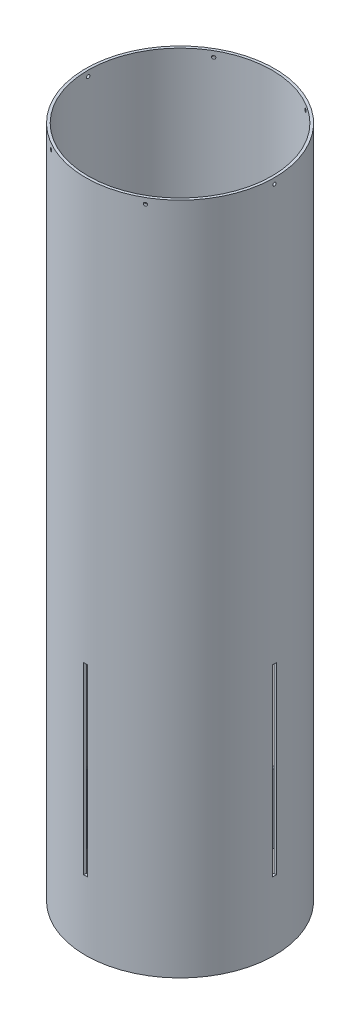
SolidWorks part; units mm, degrees
material "A-Glass Fiber"
ref_plane "Front Plane" through (0, 0, 0) normal (0, 0, 1) x (1, 0, 0)
ref_plane "Top Plane" through (0, 0, 0) normal (0, 1, 0) x (1, 0, 0)
ref_plane "Right Plane" through (0, 0, 0) normal (1, 0, 0) x (0, 0, -1)
sketch "Sketch1" plane through (0, 0, 0) normal (0, 1, 0) x (1, 0, 0)
  circle A0 centre (0, 0) radius 76.2
  circle A1 centre (0, 0) radius 78.359
  dimension "D1" = 152.4
  dimension "D2" = 156.718
extrude "Boss-Extrude1" add sketch "Sketch1" along normal blind 558.8
ref_plane "Plane1" through (0, 0, 0) normal (0.7071, 0, 0.7071) x (0.7071, 0, -0.7071)
ref_axis "Axis1" through (0, 558.8, 0) along (0, -1, 0)
sketch "Sketch2" plane through (0, 0, 0) normal (1, 0, 0) x (0, 0, -1)
  line L0 (0, 0) -> (0, 57.15)
  line L1 (1.5875, 57.15) -> (-1.5875, 57.15)
  line L2 (1.5875, 57.15) -> (1.5875, 209.55)
  line L3 (1.5875, 209.55) -> (-1.5875, 209.55)
  line L4 (-1.5875, 57.15) -> (-1.5875, 209.55)
  line L5 (1.5875, 57.15) -> (-1.5875, 209.55) construction
  line L6 (1.5875, 209.55) -> (-1.5875, 57.15) construction
  line L7 (78.359, 558.8) -> (-78.359, 558.8) construction
  line L8 (78.359, 558.8) -> (-78.359, 558.8)
  line L9 (0, 558.8) -> (0, 554.0375)
  circle A0 centre (0, 554.0375) radius 1.3525
  point P0 (0, 133.35)
  dimension "D4" = 2.7051
  dimension "D1" = 3.175
  dimension "D2" = 152.4
  dimension "D3" = 57.15
  dimension "D5" = 4.7625
extrude "Cut-Extrude1" cut sketch "Sketch2" against normal through all contours L4 L1 L2 L3 region at (0, 133.35, 0)
pattern_circular "CirPattern1" count 4 over 360 about axis through (0, 0, 0) along (0, 1, 0) of "Cut-Extrude1" reverse direction yes
extrude "Cut-Extrude2" cut sketch "Sketch2<3>" against normal through all contours A0 region at (0, 553.1082, 0.9293)
sketch "Sketch2<3>" plane through (0, 0, 0) normal (1, 0, 0) x (0, 0, -1) same geometry as "Sketch2"
pattern_circular "CirPattern2" count 6 over 360 about axis through (0, 558.8, 0) along (0, -1, 0) of "Cut-Extrude2"
sketch "Sketch3" plane through (0, 0, 0) normal (0.7071, 0, 0.7071) x (0.7071, 0, -0.7071)
  line L0 (0, 0) -> (0, 127) construction
  circle A0 centre (0, 127) radius 3.175
  dimension "D1" = 6.35
  dimension "D2" = 127
extrude "Cut-Extrude3" cut sketch "Sketch3" against normal through all
equation "\"Aft_Lower_Length\"= 22in"
equation "\"D1@Boss-Extrude1\"=\"Aft_Lower_Length\""
equation "\"AB_Coupler_OD_Length\"= 1in"
equation "\"AB_Coupling_Section_Length\"= 0.375in"
equation "\"AB_Coupler_Length\"= \"AB_Coupler_OD_Length\" + \"AB_Coupling_Section_Length\" * 2"
equation "\"AB_Coupler_Num_Screws\"= 6"
equation "\"AB_Coupling_Screw_Diameter\"= 0.1065in"
equation "\"Aft_Upper_Length\"= \"Aft_Section_Length\" - \"Aft_Lower_Length\" - \"AB_Coupler_OD_Length\""
equation "\"Aft_Section_Length\"= 40in"
equation "\"D4@Sketch2\"=\"AB_Coupling_Screw_Diameter\""
equation "\"D5@Sketch2\"=\"AB_Coupling_Section_Length\"/2"
equation "\"D1@CirPattern2\"=\"AB_Coupler_Num_Screws\""
equation "\"Rail_Nut_From_Bottom\"= 5in"
equation "\"Rail_Nut_Diam\"= 0.25in"
equation "\"D1@Sketch3\"=\"Rail_Nut_Diam\""
equation "\"D2@Sketch3\"=\"Rail_Nut_From_Bottom\""
